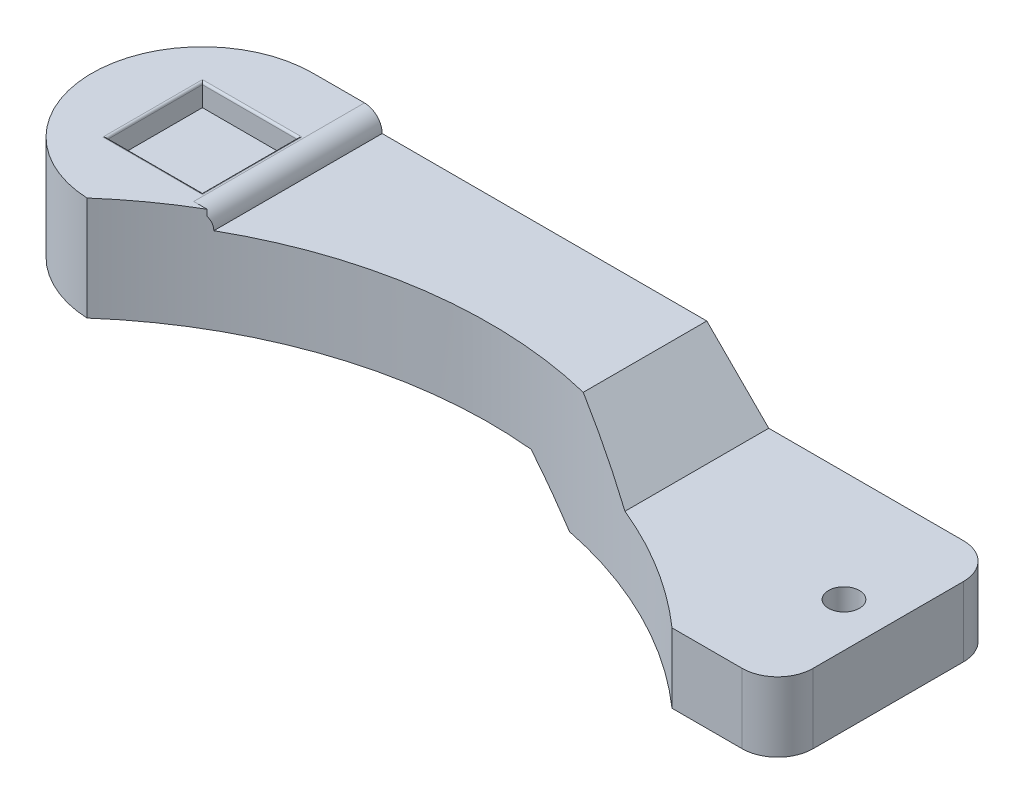
SolidWorks part; units mm, degrees
ref_plane "Front Plane" through (0, 0, 0) normal (0, 0, 1) x (1, 0, 0)
ref_plane "Top Plane" through (0, 0, 0) normal (0, 1, 0) x (1, 0, 0)
ref_plane "Right Plane" through (0, 0, 0) normal (1, 0, 0) x (0, 0, -1)
sketch "Sketch1" plane through (0, 0, 0) normal (0, 1, 0) x (1, 0, 0)
  line L1 (-45, 12.5) -> (45, 12.5)
  line L2 (-45, 12.5) -> (-45, -12.5)
  line L3 (-45, -12.5) -> (45, -12.5)
  line L4 (45, 12.5) -> (45, -12.5)
  dimension "D1" = 90
  dimension "D2" = 45
  dimension "D3" = 25
  dimension "D4" = 12.5
extrude "Boss-Extrude1" add sketch "Sketch1" along normal blind 16.87
sketch "Sketch3" plane through (0, 16.87, 0) normal (0, 1, 0) x (1, 0, 0)
  line L0 (-45, 12.5) -> (-45, -12.5) construction
  line L1 (-37.875, 5.375) -> (-27.125, 5.375)
  line L2 (-37.875, 5.375) -> (-37.875, -5.375)
  line L3 (-37.875, -5.375) -> (-27.125, -5.375)
  line L4 (-27.125, 5.375) -> (-27.125, -5.375)
  line L7 (-45, -12.5) -> (45, -12.5) construction
  point P4 (-32.5, 5.375)
  point P6 (-27.125, 0)
  dimension "D1" = 10.75
  dimension "D2" = 10.75
  dimension "D3" = 12.5
  dimension "D4" = 12.5
extrude "Cut-Extrude2" cut sketch "Sketch3" against normal blind 2.5
sketch "Esquisse2" plane through (0, 0, 12.5) normal (0, 0, 1) x (1, 0, 0)
  line L0 (10, 16.87) -> (19, 7.87)
  line L1 (45, 16.87) -> (10, 16.87)
  line L2 (45, 16.87) -> (45, 7.87)
  line L3 (45, 7.87) -> (10, 7.87)
  line L4 (10, 16.87) -> (10, 7.87)
  line L5 (-45, 0) -> (10, 0)
  line L8 (10, 0) -> (10, 7.87)
  line L9 (10, 0) -> (4.88, 5.12)
  line L10 (4.88, 5.12) -> (-45, 5.12)
  line L11 (-45, 5.12) -> (-45, 0)
  line M3 (-45, 0) -> (45, 0)
  line M4 (45, 0) -> (45, 16.87)
  line M5 (45, 16.87) -> (-45, 16.87)
  line M6 (-45, 16.87) -> (-45, 0)
  dimension "D1" = 35
  dimension "D2" = 9
  dimension "D3" = 45
  dimension "D4" = 45
  dimension "D5" = 2.75
extrude "Enlèv. mat.-Extru.1" cut sketch "Esquisse2" against normal blind 34 contours L8 M3 M6 | L4 L3 M5 M4 region at (29.6393, 12.5913, 12.5) region at (-18.7592, 2.5183, 12.5)
fillet "Fillet1" 2 edges at (-45, 10.995, 12.5) (-45, 10.995, -12.5) type full round first side face at (5.485, 7.465, 12.5) second side face at (5.485, 7.465, -12.5) middle face at (-45, 10.995, 0)
sketch "Esquisse5" plane through (0, 0, 0) normal (0, -1, 0) x (-1, 0, 0)
  line L0 (-45, -12.5) -> (-45, 12.5) construction
  circle A0 centre (-40, 0) radius 1.75
  dimension "D2" = 3.5
  dimension "D1" = 5
extrude "Enlèv. mat.-Extru.4" cut sketch "Esquisse5" against normal through all
fillet "Fillet3" radius 4 2 edges at (45, 3.935, -12.5) (45, 3.935, 12.5)
sketch "Sketch8" plane through (0, 16.87, 0) normal (0, 1, 0) x (1, 0, 0)
  line L1 (-24.6881, 14.1476) -> (13.3414, 14.1476)
  line L2 (-24.6881, 14.1476) -> (-24.6881, -6.796)
  line L3 (-24.6881, -6.796) -> (13.3414, -6.796)
  line L4 (13.3414, 14.1476) -> (13.3414, -6.796)
  dimension "D1" = 38.0295
  dimension "D2" = 20.9436
  dimension "D3" = 14.1476
  dimension "D4" = 24.6881
extrude "Cut-Extrude6" cut sketch "Sketch8" against normal blind 2
fillet "Fillet6" radius 2 1 edges at (-24.6881, 16.87, -2.852)
fillet "Fillet7" radius 0.25 4 edges at (-32.5, 16.87, 5.375) (-32.5, 16.87, -5.375) (-37.875, 16.87, 0) (-27.125, 16.87, 0)
sketch "Esquisse17" plane through (0, 5.12, 0) normal (0, -1, 0) x (1, 0, 0)
  circle A0 centre (-32.5, 0) radius 6.45
  dimension "D1" = 12.9
extrude "Enlèv. mat.-Extru.7" cut sketch "Esquisse17" against normal blind 3.6
sketch "Esquisse18" plane through (0, 0, 0) normal (0, 1, 0) x (1, 0, 0)
  circle A0 centre (0, -50) radius 50
  dimension "D2" = 100
  dimension "D1" = 50
extrude "Enlèv. mat.-Extru.8" cut sketch "Esquisse18" against normal through all and the other way through all
